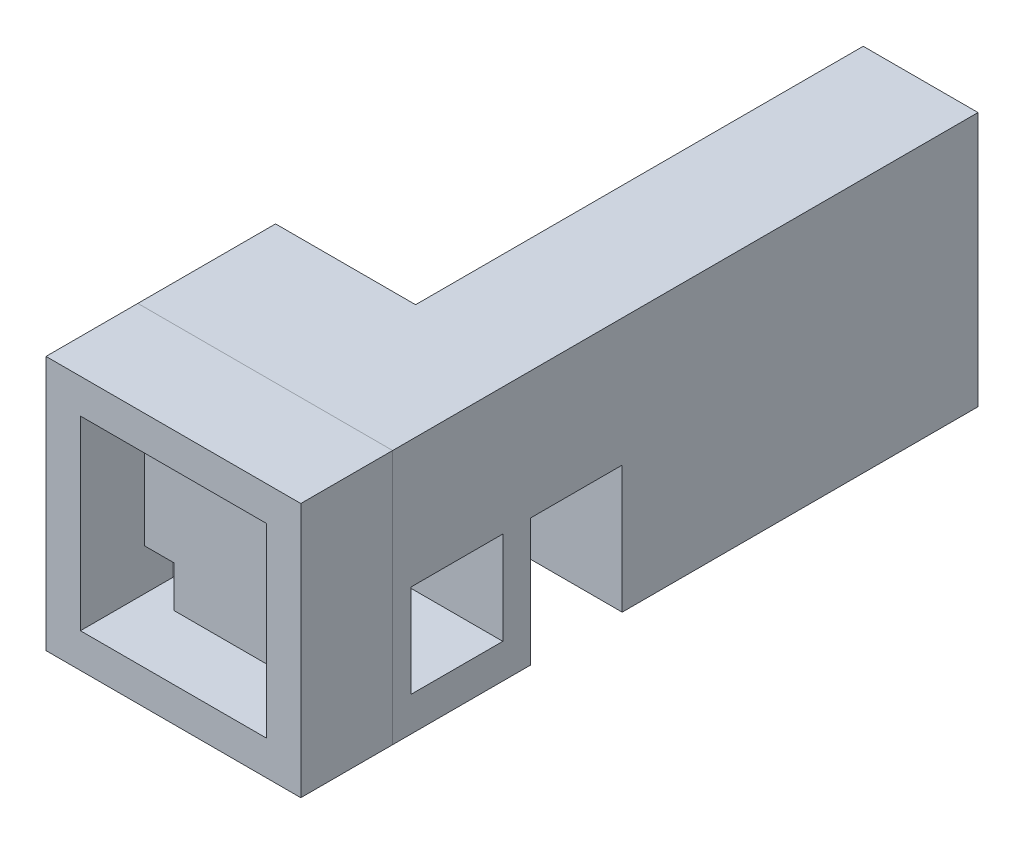
SolidWorks part; units mm, degrees
ref_plane "Front Plane" through (0, 0, 0) normal (0, 0, 1) x (1, 0, 0)
ref_plane "Top Plane" through (0, 0, 0) normal (0, 1, 0) x (1, 0, 0)
ref_plane "Right Plane" through (0, 0, 0) normal (1, 0, 0) x (0, 0, -1)
sketch "Sketch2" plane through (0, 0, 0) normal (0, 0, 1) x (1, 0, 0)
  line L0 (4.05, 8.1) -> (4.05, 9.6) construction
  line L1 (0, 0) -> (8.1, 0)
  line L2 (0, 0) -> (0, 8.1)
  line L3 (0, 8.1) -> (8.1, 8.1)
  line L4 (8.1, 0) -> (8.1, 8.1)
  line L5 (4.6, 9.6) -> (9.6, 9.6)
  line L6 (4.6, 9.6) -> (4.6, -1.5)
  line L7 (4.6, -1.5) -> (9.6, -1.5)
  line L8 (9.6, 9.6) -> (9.6, -1.5)
  line L9 (9.6, -1.5) -> (-1.5, -1.5)
  line L10 (9.6, -1.5) -> (9.6, 9.6)
  line L11 (9.6, 9.6) -> (-1.5, 9.6)
  line L12 (-1.5, -1.5) -> (-1.5, 9.6)
  line L13 (8.1, 4.05) -> (9.6, 4.05) construction
  line L14 (0, 4.05) -> (-1.5, 4.05) construction
  line L15 (-1.5, 4.05) -> (0, 4.05) construction
  line L16 (4.05, 0) -> (4.05, -1.5) construction
  line L17 (4.05, -1.5) -> (4.05, 0) construction
  point P9 (11.1, 4.05)
  point P21 (19.4332, 15.8454)
  point P22 (4.05, 11.1)
  point P23 (11.1, 4.05)
  point P24 (4.05, -3)
  point P25 (4.05, 0)
  point P26 (0, 4.05)
  dimension "D1" = 8.1
  dimension "D2" = 5
  dimension "D3" = 1.5
extrude "Boss-Extrude1" add sketch "Sketch2" along normal blind 19.5 contours L8 L5 L6 L3 L4 L1 L7 | L3 L6 L1 L4 region at (6.35, 4.05, 0) region at (6.35, -0.1217, 0)
extrude "Boss-Extrude2" add sketch "Sketch2<3>" along normal blind 1.2 from surface contours L9 L17 L1 L2 L15 L12 | L12 L15 L2 L3 L6 L11 | L6 L3 L2 L1 | L17 L9 L6 L1 | L8 L5 L6 L3 L4 L1 L7 | L3 L6 L1 L4 region at (2.3, 4.05, 0) region at (2.3, -0.1267, 0) region at (6.35, 4.05, 0) region at (6.35, -0.1217, 0) starting at face at (7.1, 4.05, 19.5)
sketch "Sketch2<3>" plane through (0, 0, 0) normal (0, 0, 1) x (1, 0, 0) same geometry as "Sketch2"
ref_plane "Plane3" through (0, 0, 20.7) normal (0, 0, 1) x (1, 0, 0)
extrude "Boss-Extrude3" add sketch "Sketch2<5>" along normal offset from surface (8.8 mm away) 10 from surface contours L12 L9 L6 L1 L2 L3 L11 | L8 L5 L6 L3 L4 L1 L7 region at (2.3, -0.1267, 0) region at (6.35, -0.1217, 0) up to face at (1.55, 4.05, 19.5) starting at face at (4.05, 4.05, 20.7)
sketch "Sketch2<5>" plane through (0, 0, 0) normal (0, 0, 1) x (1, 0, 0) same geometry as "Sketch2"
ref_plane "Plane2" through (0, 0, 26.7) normal (0, 0, 1) x (1, 0, 0)
extrude "Boss-Extrude4" add sketch "Sketch2<7>" against normal blind 1.2 from surface contours L12 L9 L6 L1 L2 L3 L11 | L6 L3 L2 L1 | L8 L5 L6 L3 L4 L1 L7 | L3 L6 L1 L4 region at (2.3, 4.05, 0) region at (2.3, -0.1267, 0) region at (6.35, 4.05, 0) region at (6.35, -0.1217, 0) starting at plane "Plane2"
sketch "Sketch2<7>" plane through (0, 0, 0) normal (0, 0, 1) x (1, 0, 0) same geometry as "Sketch2"
split "Split1" bodies to split 104 resulting bodies 106 108 split by face at (4.05, 4.05, 25.5)
sketch "Sketch4" plane through (0, 0, 26.7) normal (0, 0, 1) x (1, 0, 0)
  line L0 (0, 8.1) -> (0, 0) construction
  line L9 (0.9, 0.9) -> (0, 0.9) construction
  line L10 (0.9, 0.9) -> (0.9, 0) construction
  line L11 (8.1, 0) -> (0, 0) construction
  line L12 (0, 0) -> (8.1, 8.1) construction
  line L17 (1.275, 0.525) -> (0.525, 1.275) construction
  line L18 (0.525, 0.525) -> (1.275, 0.525) construction
  line L19 (0.525, 0.525) -> (0.525, 1.275) construction
  line L20 (0.525, 1.275) -> (1.275, 1.275) construction
  line L21 (1.275, 0.525) -> (1.275, 1.275) construction
  line L23 (0, 0) -> (1.275, 0)
  line L24 (0, 0) -> (0, 1.8)
  line L25 (0, 1.8) -> (1.275, 1.8)
  line L26 (1.275, 0) -> (1.275, 1.8)
  line L27 (8.1, 0) -> (6.825, 0)
  line L28 (8.1, 0) -> (8.1, 1.8)
  line L29 (8.1, 1.8) -> (6.825, 1.8)
  line L30 (6.825, 0) -> (6.825, 1.8)
  line L31 (0, 8.1) -> (1.275, 8.1)
  line L32 (0, 8.1) -> (0, 6.3)
  line L33 (0, 6.3) -> (1.275, 6.3)
  line L34 (1.275, 8.1) -> (1.275, 6.3)
  line L35 (8.1, 8.1) -> (6.825, 8.1)
  line L36 (8.1, 8.1) -> (8.1, 6.3)
  line L37 (8.1, 6.3) -> (6.825, 6.3)
  line L38 (6.825, 8.1) -> (6.825, 6.3)
  dimension "D1" = 0.9
  dimension "D2" = 0.75
  dimension "D3" = 1.8
extrude "Cut-Extrude1" cut sketch "Sketch4" against normal up to surface (1.2 mm away) up to face at (4.05, 4.05, 25.5)
sketch "Sketch5" plane through (4.6, 0, 0) normal (-1, 0, 0) x (0, 0, 1)
  line L0 (0, 9.6) -> (0, -1.5) construction
  line L1 (19.5, -1.5) -> (15.5, -1.5)
  line L2 (19.5, -1.5) -> (19.5, 4.05)
  line L3 (19.5, 4.05) -> (15.5, 4.05)
  line L4 (15.5, -1.5) -> (15.5, 4.05)
  point P7 (0, 4.05)
  dimension "D1" = 4
extrude "Cut-Extrude2" cut sketch "Sketch5" against normal through all
sketch "Sketch6" plane through (0, 0, 20.7) normal (0, 0, 1) x (1, 0, 0)
  line L0 (9.6, -1.5) -> (9.6, 4.05) construction
  line L1 (9.6, 0) -> (8.1, 0)
  line L2 (9.6, 0) -> (9.6, 4.05)
  line L3 (9.6, 4.05) -> (8.1, 4.05)
  line L4 (8.1, 0) -> (8.1, 4.05)
  line L5 (8.1, 0) -> (0, 0) construction
  line L6 (9.6, 4.05) -> (4.6, 4.05) construction
  line L7 (8.1, 8.1) -> (8.1, 0) construction
extrude "Cut-Extrude3" cut sketch "Sketch6" along normal blind 4
